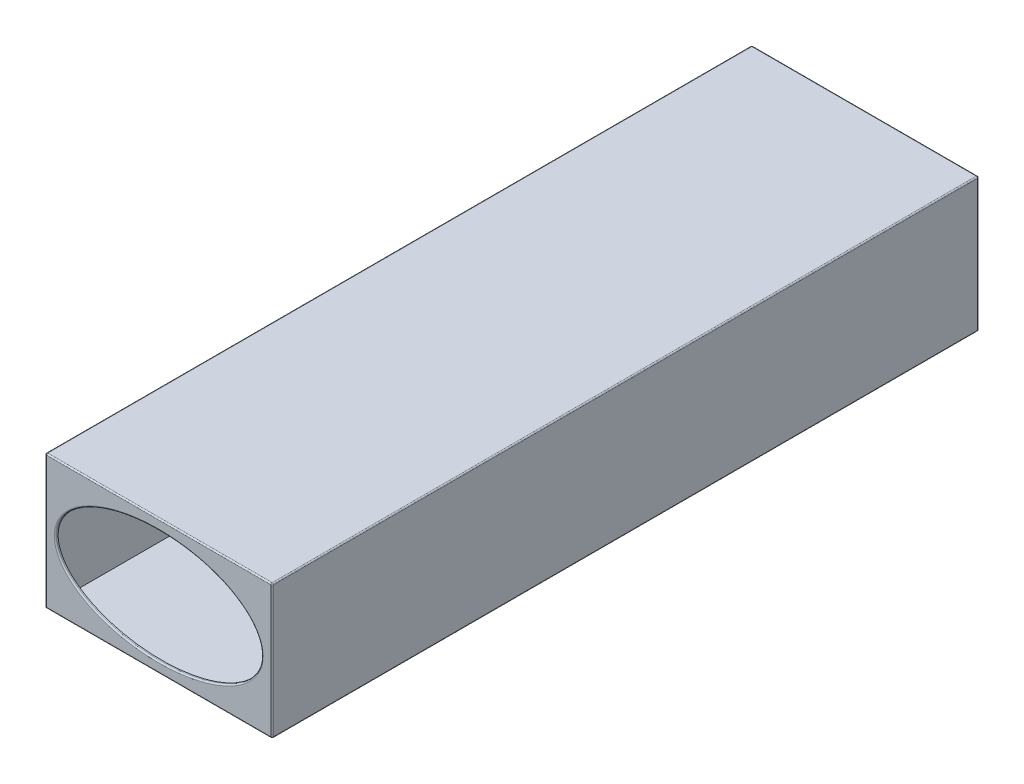
SolidWorks part; units mm, degrees
ref_plane "Front Plane" through (0, 0, 0) normal (0, 0, 1) x (1, 0, 0)
ref_plane "Top Plane" through (0, 0, 0) normal (0, 1, 0) x (1, 0, 0)
ref_plane "Right Plane" through (0, 0, 0) normal (1, 0, 0) x (0, 0, -1)
sketch "Sketch1" plane through (0, 0, 0) normal (0, 1, 0) x (1, 0, 0)
  line L1 (-22, -68.5) -> (22, -68.5)
  line L2 (-22, -68.5) -> (-22, 68.5)
  line L3 (-22, 68.5) -> (22, 68.5)
  line L4 (22, -68.5) -> (22, 68.5)
  line L5 (-22, -68.5) -> (22, 68.5) construction
  line L6 (-22, 68.5) -> (22, -68.5) construction
  point P0 (0, 0)
  dimension "D1" = 44
  dimension "D2" = 137
extrude "Boss-Extrude1" add sketch "Sketch1" along normal blind 26
sketch "Sketch2" plane through (0, 0, 68.5) normal (0, 0, 1) x (1, 0, 0)
  line L0 (-22, 26) -> (-22, 0) construction
  line L1 (-22, 13) -> (-24.6502, 13) construction
  line L2 (0, 26) -> (0, 28.0783) construction
  line L3 (-22, 26) -> (22, 26) construction
  ellipse E0 centre (0, 13) end of major axis (20, 13) minor radius 11
  dimension "D1" = 22
  dimension "D2" = 40
extrude "Cut-Extrude1" cut sketch "Sketch2" against normal blind 0.5
shell "Shell1" thickness 0.5 removed face at (20, 13, 68)
fillet "Fillet1" radius 0.25 13 edges at (0, 0, -68.5) (-22, 13, -68.5) (-22, 0, 0) (22, 13, -68.5) (22, 0, 0) (-22, 13, 68.5) (22, 13, 68.5) (0, 0, 68.5) (20, 13, 68.5) (0, 26, 68.5) (-22, 26, 0) (0, 26, -68.5) (22, 26, 0)
